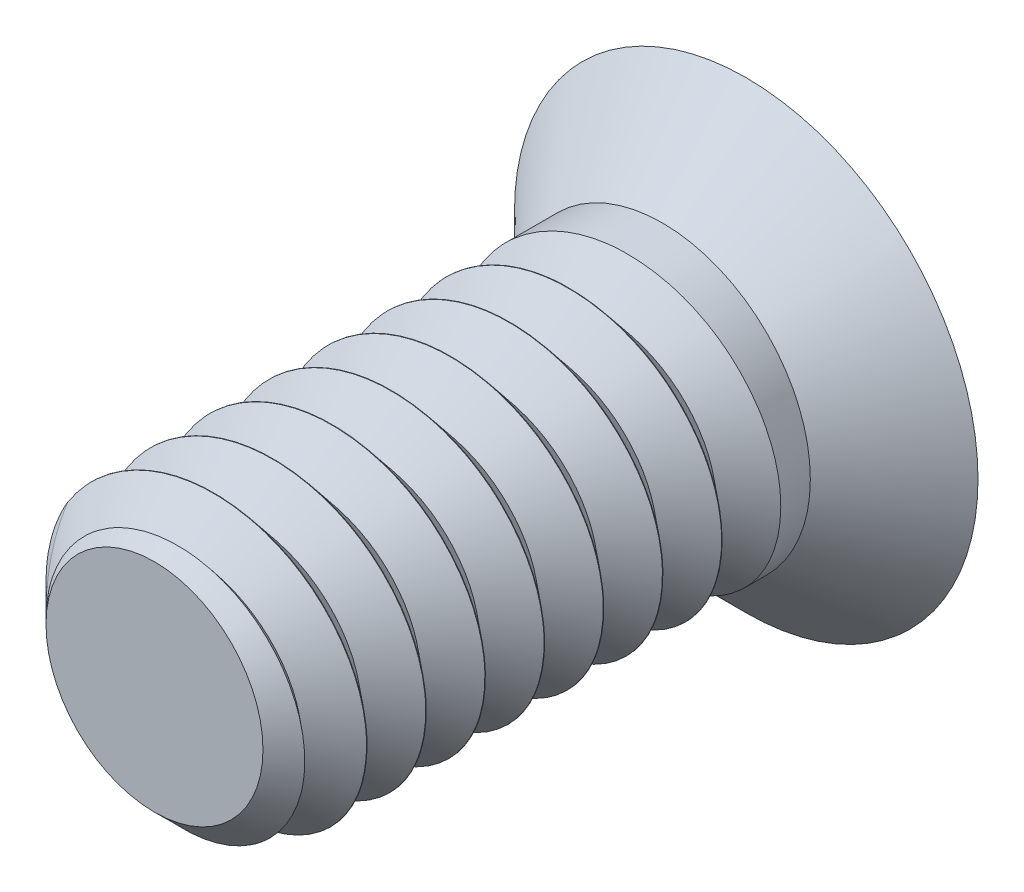
SolidWorks part; units mm, degrees
ref_plane "Front Plane" through (0, 0, 0) normal (0, 0, 1) x (1, 0, 0)
ref_plane "Top Plane" through (0, 0, 0) normal (0, 1, 0) x (1, 0, 0)
ref_plane "Right Plane" through (0, 0, 0) normal (1, 0, 0) x (0, 0, -1)
sketch "Sketch1" plane through (0, 0, 0) normal (0, 0, 1) x (1, 0, 0)
  circle A0 centre (0, 0) radius 3
  dimension "D1" = 6
extrude "Boss-Extrude1" add sketch "Sketch1" along normal blind 10
ref_plane "Plane4" through (0, 0, 0.6) normal (0, 0, 1) x (1, 0, 0)
chamfer "Chamfer3" distance 0.8 angle 45 1 edges at (3, 0, 10)
sketch "Sketch2" plane through (0, 0, 0.6) normal (0, 0, -1) x (-1, 0, 0)
  circle A0 centre (0, 0) radius 3
  circle A2 centre (0, 0) radius 3 construction
curve "Helix/Spiral1" pitch 1.2 height 35 turns 29.1667
sketch "Sketch3" plane through (0, 0, 0) normal (1, 0, 0) x (0, 0, -1)
  line L0 (-1.195, -3) -> (-0.005, -3)
  line L1 (-0.005, -3) -> (-0.6, -2.28)
  line L2 (-0.6, -2.28) -> (-1.195, -3)
  line L3 (-0.01, -3) -> (-9.2, -3) construction
  line L4 (-0.6, 5.17) -> (-0.6, -5.17) construction
  point P3 (-0.6, -3)
  dimension "D2" = 0.72
  dimension "D1" = 1.19
sweep "Cut-Sweep3" cut profiles "Sketch3" path "Helix/Spiral1" align with end faces yes
sketch "Sketch5" plane through (0, 0, 0) normal (0, 0, -1) x (-1, 0, 0)
  circle A0 centre (0, 0) radius 4.9
  dimension "D1" = 9.8
extrude "Boss-Extrude2" add sketch "Sketch5" along normal blind 2
sketch "Sketch4" plane through (0, 0, -2) normal (0, 0, -1) x (-1, 0, 0)
  line L21 (1.04, -1.04) -> (-1.04, -1.04)
  line L22 (1.04, -1.04) -> (1.04, 1.04)
  line L23 (1.04, 1.04) -> (-1.04, 1.04)
  line L24 (-1.04, -1.04) -> (-1.04, 1.04)
  line L25 (1.04, -1.04) -> (-1.04, 1.04) construction
  line L26 (1.04, 1.04) -> (-1.04, -1.04) construction
  point P0 (0, 0)
  point P6 (0, 0)
  dimension "D1" = 2.08
extrude "Cut-Extrude1" cut sketch "Sketch4" against normal blind 3
chamfer "Chamfer2" distance 2.2 angle 45 1 edges at (-4.9, 0, 0)
equation "\"cleatShaftLen\" = 3"
equation "\"cleatHeadLen\" = 4mm"
equation "\"cleatHeadGirth\" = 12mm"
equation "\"cleatShaftGirth\" = 8mm"
equation "\"cleatTolOffset\" = 0.4mm"
equation "\"cleatCham\" = 1mm"
equation "\"cleatSpacing\" = 30mm"
equation "\"cleatTriangleAngle\" = 25deg"
equation "\"cleatMinimumTriangleAngle\" = 12deg"
equation "\"nCleats\" = 2"
equation "\"threadID\" = 8.3mm"
equation "\"threadPitch\" = 2mm"
equation "\"threadOD\" = 10.7mm"
equation "\"cleatFemShaftLen\" = \"cleatShaftLen\" - \"cleatTolOffset\""
equation "\"cleatFemHeadLen\" = \"cleatHeadLen\" + \"cleatTolOffset\" * 1.25"
equation "\"cleatFemHeadGirth\" = \"cleatHeadGirth\" + \"cleatTolOffset\""
equation "\"cleatFemShaftGirth\" = \"cleatShaftGirth\" + \"cleatTolOffset\""
equation "\"lip\" = 2mm"
equation "\"cubeCham\" = 0.7mm"
equation "\"cubeCutoutPadding\" = 3mm"
equation "\"wall\" = 3mm"
equation "\"cleatLen\" = \"cleatShaftLen\" + \"cleatHeadLen\""
equation "\"coverThickness\" = 2mm"
equation "\"plugDepth\" = 4mm"
equation "\"bottomChamOffset\" = 1.8mm"
equation "\"maleHelperAngle\" = 45deg"
equation "\"maleHelperAngle2\" = 35deg"
equation "\"stFactor\" = 0.6"
equation "\"stID\" = \"threadID\" * \"stFactor\""
equation "\"stOD\" = \"threadOD\" * \"stFactor\""
equation "\"stPitch\" = \"threadPitch\" * \"stFactor\""
equation "\"temp\" = 0"
equation "\"threadMaleOD\" = 10.0mm"
equation "\"stMaleOD\" = \"threadMaleOD\" * \"stFactor\""
equation "\"D1@Sketch1\"=\"stMaleOD\""
equation "\"D1@Boss-Extrude1\"=10mm"
equation "\"D2@Sketch3\"=(\"stOD\"-\"stID\")/2"
equation "\"D1@Sketch3\"=\"stPitch\"-0.01"
equation "\"D1@Boss-Extrude2\"= \"stSocketHeadLen\""
equation "\"stProtrusion\" = (\"stOD\" - \"stID\") / 2"
equation "\"stHexDiam\" = 2.5mm"
equation "\"stHexPad\" = 0.08mm"
equation "\"stSocketHeadProtrusion\" = 0.65mm"
equation "\"stSocketHeadLen\" = 1.2mm"
equation "\"stSocketHeadLenPad\" = 0.1mm"
equation "\"stSocketHeadCounterboreDepth\" = \"stSocketHeadLen\" + \"stSocketHeadLenPad\""
equation "\"stDriverDepth\" = 2mm"
equation "\"stNutODPad\" = 3mm"
equation "\"stNutDiam\" = \"stOD\" + \"stNutODPad\""
equation "\"stNutHeight\" = 3mm"
equation "\"stNutCham\" = 0.4mm"
equation "\"stSocketHeadDiam\" = \"stOD\" + \"stSocketHeadProtrusion\""
equation "\"threadMaleSocketDiam\" = 15.0mm"
equation "\"threadMaleHex\" = 6mm"
equation "\"wall2\" = 4.15mm"
equation "\"plugCornerFill\" = 3mm"
